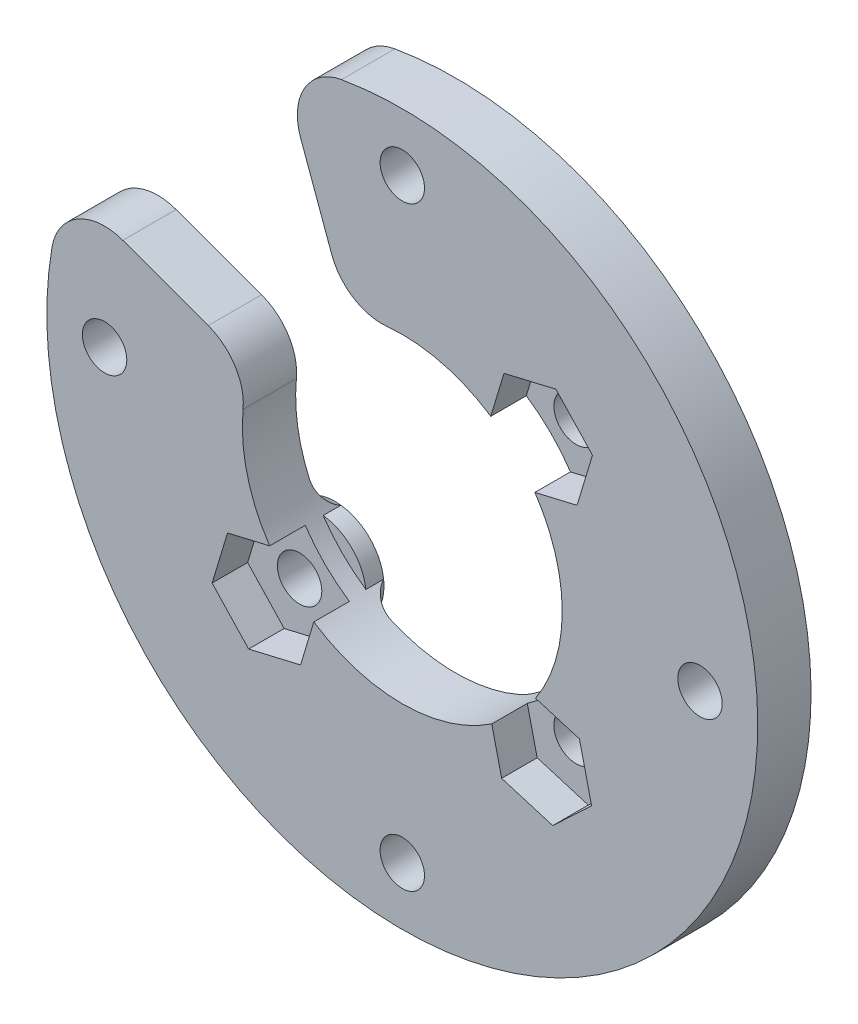
SolidWorks part; units mm, degrees
ref_plane "前视基准面" through (0, 0, 0) normal (0, 0, 1) x (1, 0, 0)
ref_plane "上视基准面" through (0, 0, 0) normal (0, 1, 0) x (1, 0, 0)
ref_plane "右视基准面" through (0, 0, 0) normal (1, 0, 0) x (0, 0, -1)
sketch "草图1" plane through (0, 0, 0) normal (0, 0, 1) x (1, 0, 0)
  circle A0 centre (0, 0) radius 16.75 construction
  circle A1 centre (0, 16.75) radius 1.25
  circle A2 centre (16.75, 0) radius 1.25
  circle A3 centre (0, -16.75) radius 1.25
  circle A4 centre (-16.75, 0) radius 1.25
  circle A5 centre (0, 16.75) radius 2.3
  circle A6 centre (16.75, 0) radius 2.3
  circle A7 centre (0, -16.75) radius 2.3
  circle A8 centre (-16.75, 0) radius 2.3
  circle A9 centre (0, 0) radius 20
  circle A10 centre (0, 0) radius 9
  dimension "D2" = 2.5
  dimension "D3" = 33.5
  dimension "D4" = 4.6
  dimension "D5" = 4
  dimension "D6" = 40
  dimension "D7" = 18
  dimension "D1" = 4
extrude "凸台-拉伸5" add sketch "草图1" along normal blind 3 contours A9 A10 A6 A7 A8 A5 | A10 A8 A4 | A10 A5 A1 | A10 A6 A2 | A10 A7 A3 region at (-2.2349, 16.75, 0) region at (14.5151, 0, 0) region at (-2.2349, -16.75, 0) region at (-18.9849, 0, 0) region at (-19.4343, 0, 0)
extrude "切除-拉伸1" cut sketch "草图1<6>" along normal blind 1.1 contours A10 A6 A2 | A10 A5 A1 | A10 A8 A4 | A10 A7 A3 region at (-2.2349, 16.75, 0) region at (14.5151, 0, 0) region at (-2.2349, -16.75, 0) region at (-18.9849, 0, 0)
sketch "草图1<6>" plane through (0, 0, 0) normal (0, 0, 1) x (1, 0, 0) same geometry as "草图1"
sketch "草图2" plane through (0, 0, 0) normal (0, 0, 1) x (1, 0, 0)
  line L0 (0, 0) -> (-7.7782, 7.7782) construction
  circle A0 centre (0, 0) radius 11 construction
  circle A1 centre (-7.7782, 7.7782) radius 1.25
  circle A2 centre (7.7782, 7.7782) radius 1.25
  circle A3 centre (7.7782, -7.7782) radius 1.25
  circle A4 centre (-7.7782, -7.7782) radius 1.25
  dimension "D1" = 22
  dimension "D2" = 2.5
  dimension "D3" = 4
extrude "切除-拉伸2" cut sketch "草图2" along normal blind 31
ref_plane "基准面1" through (0, 0, 0) normal (0, 0, -1) x (-1, 0, 0)
sketch "草图3" plane through (0, 0, 0) normal (0, 0, -1) x (-1, 0, 0)
  circle A0 centre (7.7782, 7.7782) radius 2.75
  circle A1 centre (7.7782, -7.7782) radius 2.75
  circle A2 centre (-7.7782, -7.7782) radius 2.75
  circle A3 centre (-7.7782, 7.7782) radius 2.75
  circle A4 centre (7.7782, 7.7782) radius 1.25
  circle A5 centre (7.7782, -7.7782) radius 1.25
  circle A6 centre (-7.7782, -7.7782) radius 1.25
  circle A7 centre (-7.7782, 7.7782) radius 1.25
  dimension "D3" = 1.5
  dimension "D1" = 4
  dimension "D2" = 4
extrude "凸台-拉伸6" add sketch "草图3" along normal blind 1
fillet "圆角1" radius 1.5 4 edges at (9.7227, -9.7227, 0) (-9.7227, -9.7227, 0) (-9.7227, 9.7227, 0) (9.7227, 9.7227, 0)
ref_plane "基准面2" through (0, 0, 3) normal (0, 0, 1) x (1, 0, 0)
sketch "草图4" plane through (0, 0, 3) normal (0, 0, 1) x (1, 0, 0)
  line L0 (6.9114, 4.9038) -> (9.8341, 5.5903)
  line L1 (-8.4647, 10.7008) -> (-10.6525, 8.645)
  line L2 (-10.6525, 8.645) -> (-9.966, 5.7223)
  line L3 (-9.966, 5.7223) -> (-7.0917, 4.8555)
  line L4 (-7.0917, 4.8555) -> (-4.9038, 6.9114)
  line L5 (-4.9038, 6.9114) -> (-5.5903, 9.8341)
  line L6 (-5.5903, 9.8341) -> (-8.4647, 10.7008)
  line L7 (9.8341, 5.5903) -> (10.7008, 8.4647)
  line L8 (8.645, 10.6525) -> (5.7223, 9.966)
  line L9 (10.7008, 8.4647) -> (8.645, 10.6525)
  line L10 (5.7223, 9.966) -> (4.8555, 7.0917)
  line L11 (4.8555, 7.0917) -> (6.9114, 4.9038)
  line L12 (4.9038, -6.9114) -> (5.5903, -9.8341)
  line L13 (5.5903, -9.8341) -> (8.4647, -10.7008)
  line L14 (10.6525, -8.645) -> (9.966, -5.7223)
  line L15 (8.4647, -10.7008) -> (10.6525, -8.645)
  line L16 (9.966, -5.7223) -> (7.0917, -4.8555)
  line L17 (7.0917, -4.8555) -> (4.9038, -6.9114)
  line L18 (-6.9114, -4.9038) -> (-9.8341, -5.5903)
  line L19 (-9.8341, -5.5903) -> (-10.7008, -8.4647)
  line L20 (-8.645, -10.6525) -> (-5.7223, -9.966)
  line L21 (-10.7008, -8.4647) -> (-8.645, -10.6525)
  line L22 (-5.7223, -9.966) -> (-4.8555, -7.0917)
  line L23 (-4.8555, -7.0917) -> (-6.9114, -4.9038)
  circle A0 centre (-7.7782, 7.7782) radius 2.6 construction
  dimension "D1" = 5.2
  dimension "D2" = 4
extrude "切除-拉伸3" cut sketch "草图4" against normal blind 2
sketch "草图5" plane through (0, 0, 0) normal (0, 0, -1) x (-1, 0, 0)
  line L0 (0, 0) -> (8.702, 23.9086)
  line L1 (0, 0) -> (23.9086, 8.702)
  line L2 (0, 0) -> (24.1838, 24.1838) construction
  circle A0 centre (0, 0) radius 25.443
  point P6 (23.9086, 8.702)
  circle M4 centre (0, 0) radius 20
  arc M13 (-3.6387, 8.2316) -> (3.6387, 8.2316) centre (0, 0) cw
  arc M14 (3.6387, 8.2316) -> (8.2316, 3.6387) centre (7.7782, 7.7782) cw
  arc M15 (8.2316, 3.6387) -> (8.2316, -3.6387) centre (0, 0) cw
  dimension "D1" = 25
  dimension "D2" = 25
extrude "切除-拉伸4" cut sketch "草图5" against normal through all both and the other way through all contours L2 L1 M14 M15 M4 | L2 L0 M14 M4 M13 | L0 L2 M14 M13 | L2 L1 M15 M14 region at (-7.5614, 5.2717, 0) region at (-5.2717, 7.5614, 0) region at (-8.6653, 14.2075, 0) region at (-14.2075, 8.6653, 0)
fillet "圆角2" radius 3 4 edges at (-18.7939, 6.8404, 1.5) (-6.8404, 18.7939, 1.5) (-8.4572, 3.0782, 1.5) (-3.0782, 8.4572, 1.5)
